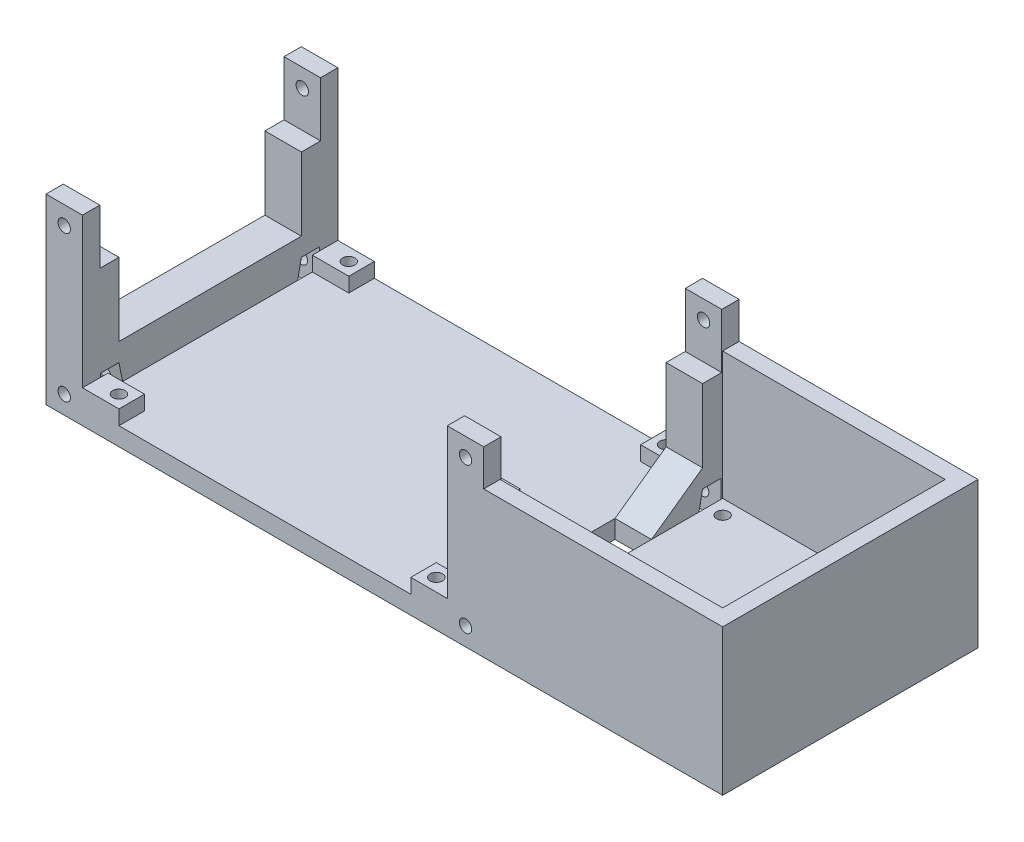
SolidWorks part; units mm, degrees
ref_plane "Front Plane" through (0, 0, 0) normal (0, 0, 1) x (1, 0, 0)
ref_plane "Top Plane" through (0, 0, 0) normal (0, 1, 0) x (1, 0, 0)
ref_plane "Right Plane" through (0, 0, 0) normal (1, 0, 0) x (0, 0, -1)
sketch "Sketch1" plane through (0, 0, 0) normal (0, 1, 0) x (1, 0, 0)
  line L1 (-60, -35) -> (60, -35)
  line L2 (-60, -35) -> (-60, 35)
  line L3 (-60, 35) -> (60, 35)
  line L4 (60, -35) -> (60, 35)
  line L5 (-60, -35) -> (60, 35) construction
  line L6 (-60, 35) -> (60, -35) construction
  point P0 (0, 0)
  dimension "D1" = 120
  dimension "D2" = 70
extrude "Boss-Extrude1" add sketch "Sketch1" along normal blind 5
sketch "Sketch4" plane through (0, 5, 0) normal (0, 1, 0) x (1, 0, 0)
  line L1 (-60, -35) -> (-50, -35)
  line L2 (-60, -35) -> (-60, -25)
  line L3 (-60, -25) -> (-50, -25)
  line L4 (-50, -35) -> (-50, -25)
  line L5 (-60, 35) -> (-50, 35)
  line L6 (-60, 35) -> (-60, 25)
  line L7 (-60, 25) -> (-50, 25)
  line L8 (-50, 35) -> (-50, 25)
  line L9 (60, -35) -> (50, -35)
  line L10 (60, -35) -> (60, -25)
  line L11 (60, -25) -> (50, -25)
  line L12 (50, -35) -> (50, -25)
  line L13 (60, 35) -> (50, 35)
  line L14 (60, 35) -> (60, 25)
  line L15 (60, 25) -> (50, 25)
  line L16 (50, 35) -> (50, 25)
  dimension "D1" = 10
  dimension "D2" = 10
extrude "Boss-Extrude2" add sketch "Sketch4" along normal blind 30
sketch "Sketch5" plane through (0, 0, 0) normal (0, -1, 0) x (1, 0, 0)
  line L0 (-60, -35) -> (-60, 35) construction
  line L1 (-60, -30) -> (-50, -30)
  line L2 (-60, -30) -> (-60, -25)
  line L3 (-60, -25) -> (-50, -25)
  line L4 (-50, -30) -> (-50, -25)
  line L5 (60, 35) -> (60, -35) construction
  line L6 (-60, 30) -> (-50, 30)
  line L7 (-60, 30) -> (-60, 25)
  line L8 (-60, 25) -> (-50, 25)
  line L9 (-50, 30) -> (-50, 25)
  line L10 (60, 30) -> (50, 30)
  line L11 (60, 30) -> (60, 25)
  line L12 (60, 25) -> (50, 25)
  line L13 (50, 30) -> (50, 25)
  line L14 (60, -35) -> (-60, -35) construction
  line L15 (60, -30) -> (50, -30)
  line L16 (60, -30) -> (60, -25)
  line L17 (60, -25) -> (50, -25)
  line L18 (50, -30) -> (50, -25)
  line L19 (-60, 35) -> (60, 35) construction
  dimension "D1" = 10
  dimension "D2" = 5
  dimension "D3" = 5
  dimension "D4" = 5
extrude "Cut-Extrude2" cut sketch "Sketch5" against normal blind 10
sketch "Sketch8" plane through (0, 5, 0) normal (0, 1, 0) x (1, 0, 0)
  line L1 (-50, 35) -> (-40, 35)
  line L2 (-50, 35) -> (-50, 28)
  line L3 (-50, 28) -> (-40, 28)
  line L4 (-40, 35) -> (-40, 28)
  line L5 (-50, -35) -> (-40, -35)
  line L6 (-50, -35) -> (-50, -28)
  line L7 (-50, -28) -> (-40, -28)
  line L8 (-40, -35) -> (-40, -28)
  line L9 (50, -35) -> (40, -35)
  line L10 (50, -35) -> (50, -28)
  line L11 (50, -28) -> (40, -28)
  line L12 (40, -35) -> (40, -28)
  line L13 (50, 35) -> (40, 35)
  line L14 (50, 35) -> (50, 28)
  line L15 (50, 28) -> (40, 28)
  line L16 (40, 35) -> (40, 28)
  dimension "D1" = 7
  dimension "D2" = 10
extrude "Boss-Extrude5" add sketch "Sketch8" along normal blind 4
hole_wizard "M3 Clearance Hole2" positions "Sketch10" profile "Sketch9" hole size "M3" standard "ANSI Metric"
sketch "Sketch10" plane through (0, 9, 0) normal (0, 1, 0) x (1, 0, 0)
  line L1 (40, -35) -> (50, -35) construction
  line L2 (-50, -30) -> (-50, -28) construction
  point P0 (-43.5, -31.5)
  point P2 (-43.5, 31.5)
  point P4 (43.5, 31.5)
  point P6 (43.5, -31.5)
  dimension "D1" = 87
  dimension "D2" = 63
  dimension "D3" = 3.5
  dimension "D4" = 6.5
sketch "Sketch9" plane through (-43.5, 9, 31.5) normal (1, 0, 0) x (0, 0, 1)
  line L0 (0, 0) -> (0, 66.0215)
  line L1 (0, 66.0215) -> (1.7, 65)
  line L2 (1.7, 65) -> (1.7, 0)
  line L5 (1.7, 0) -> (0, 0)
  line L10 (0, 66.0215) -> (-1.7, 65) construction
  line L11 (0, -6.35) -> (0, 107.95) construction
  dimension "Hole Dia." = 3.4
  dimension "Hole Depth" = 65
  dimension "Drill Angle" = 118
sketch "Sketch12" plane through (0, 0, 0) normal (0, -1, 0) x (1, 0, 0)
  line L1 (125.5, 35) -> (60, 35)
  line L2 (125.5, 35) -> (125.5, -35)
  line L3 (125.5, -35) -> (60, -35)
  line L4 (60, 35) -> (60, -35)
  line L5 (125.5, 35) -> (60, -35) construction
  line L6 (125.5, -35) -> (60, 35) construction
  line L7 (60, 25) -> (60, -25) construction
  point P0 (92.75, 0)
  dimension "D1" = 65.5
  dimension "D2" = 70
extrude "Boss-Extrude6" add sketch "Sketch12" against normal blind 5
sketch "Sketch13" plane through (0, 5, 0) normal (0, 1, 0) x (1, 0, 0)
  line L1 (60, 35) -> (125.5, 35)
  line L2 (60, 35) -> (60, 30.5)
  line L3 (60, 30.5) -> (121, 30.5)
  line L4 (125.5, -35) -> (125.5, 35)
  line L5 (125.5, 35) -> (125.5, -35) construction
  line L6 (60, -35) -> (125.5, -35)
  line L7 (60, -35) -> (60, -30.5)
  line L8 (60, -30.5) -> (121, -30.5)
  line L11 (121, 30.5) -> (121, -30.5)
  dimension "D1" = 61
  dimension "D2" = 4.5
  dimension "D3" = 4.5
extrude "Boss-Extrude7" add sketch "Sketch13" along normal blind 35
hole_wizard "M3 Clearance Hole3" positions "Sketch15" profile "Sketch14" hole size "M3" standard "ANSI Metric"
sketch "Sketch15" plane through (0, 5, 0) normal (0, 1, 0) x (1, 0, 0)
  line L0 (121, -30.5) -> (60, -30.5) construction
  line L2 (60, -30) -> (60, -25) construction
  point P0 (117, -26.5)
  point P2 (117, 26.5)
  point P4 (64, 26.5)
  point P6 (64, -26.5)
  point P15 (60, -27.5)
  dimension "D1" = 53
  dimension "D2" = 53
  dimension "D3" = 4
  dimension "D4" = 4
sketch "Sketch14" plane through (117, 5, 26.5) normal (1, 0, 0) x (0, 0, 1)
  line L0 (0, 0) -> (0, 66.0215)
  line L1 (0, 66.0215) -> (1.7, 65)
  line L2 (1.7, 65) -> (1.7, 0)
  line L5 (1.7, 0) -> (0, 0)
  line L10 (0, 66.0215) -> (-1.7, 65) construction
  line L11 (0, -6.35) -> (0, 107.95) construction
  dimension "Hole Dia." = 3.4
  dimension "Hole Depth" = 65
  dimension "Drill Angle" = 118
sketch "Sketch24" plane through (0, 5, 0) normal (0, 1, 0) x (1, 0, 0)
  line L1 (-60, 25) -> (-50, 25)
  line L2 (-60, 25) -> (-60, -25)
  line L3 (-60, -25) -> (-50, -25)
  line L4 (-50, 25) -> (-50, -25)
  line L5 (60, -25) -> (50, -25)
  line L6 (60, -25) -> (60, 25)
  line L7 (60, 25) -> (50, 25)
  line L8 (50, -25) -> (50, 25)
extrude "Boss-Extrude10" add sketch "Sketch24" along normal blind 10
sketch "Sketch16" plane through (0, 15, 0) normal (0, 1, 0) x (1, 0, 0)
  line L0 (50, 25) -> (50, -25) construction
  line L1 (60, -11) -> (50, -11)
  line L2 (60, -11) -> (60, 11)
  line L3 (60, 11) -> (50, 11)
  line L4 (50, -11) -> (50, 11)
  line L6 (60, -30) -> (60, -25) construction
  line L9 (60, -25) -> (50, -25) construction
  line L10 (50, 25) -> (60, 25) construction
  dimension "D1" = 14
  dimension "D2" = 14
extrude "Cut-Extrude5" cut sketch "Sketch16" against normal through all
sketch "Sketch22" plane through (0, 0, 35) normal (0, 0, 1) x (1, 0, 0)
  line L0 (-60, 0) -> (125.5, 0) construction
  line L2 (-60, 35) -> (-60, 0) construction
  line L3 (50, 35) -> (50, 9) construction
  circle A0 centre (-55, 5) radius 1.7
  circle A1 centre (55, 5) radius 1.7
  dimension "D3" = 3.4
  dimension "D1" = 5
  dimension "D2" = 5
  dimension "D4" = 5
extrude "Cut-Extrude7" cut sketch "Sketch22" against normal blind 20
chamfer "Chamfer2" distance 14 distance2 10 2 edges at (55, 15, 11) (55, 15, -11) first distance on face at (53.75, 15, 18) first distance on face at (56.25, 15, -18)
sketch "Sketch25" plane through (0, 0, 0) normal (0, -1, 0) x (1, 0, 0)
  line L0 (-60, 25) -> (-50, 25) construction
  line L1 (-57.745, -20) -> (-52.255, -20)
  line L2 (-57.745, -20) -> (-57.745, -17)
  line L3 (-57.745, -17) -> (-52.255, -17)
  line L4 (-52.255, -20) -> (-52.255, -17)
  line L5 (52.255, -20) -> (57.745, -20)
  line L6 (52.255, -20) -> (52.255, -17)
  line L7 (52.255, -17) -> (57.745, -17)
  line L8 (57.745, -20) -> (57.745, -17)
  line L9 (52.255, 20) -> (57.745, 20)
  line L10 (52.255, 20) -> (52.255, 17)
  line L11 (52.255, 17) -> (57.745, 17)
  line L12 (57.745, 20) -> (57.745, 17)
  line L13 (-57.745, 20) -> (-52.255, 20)
  line L14 (-57.745, 20) -> (-57.745, 17)
  line L15 (-57.745, 17) -> (-52.255, 17)
  line L16 (-52.255, 20) -> (-52.255, 17)
  line L17 (-50, -25) -> (-60, -25) construction
  line L18 (-50, -25) -> (-60, -25) construction
  line L23 (55, 25) -> (55, -25) construction
  line L24 (50, 25) -> (60, 25) construction
  line L25 (60, -25) -> (50, -25) construction
  line L26 (-55, 25) -> (-55, -25) construction
  line L27 (-60, 25) -> (-50, 25) construction
  dimension "D1" = 3
  dimension "D2" = 5
  dimension "D3" = 5
  dimension "D4" = 5.49
  dimension "D5" = 2.745
  dimension "D6" = 2.745
extrude "Cut-Extrude8" cut sketch "Sketch25" against normal blind 8
sketch "Sketch26" plane through (0, 0, -35) normal (0, 0, -1) x (-1, 0, 0)
  circle A0 centre (-55, 5) radius 1.7
  circle A1 centre (55, 5) radius 1.7
  circle A2 centre (55, 5) radius 1.7 construction
  circle A3 centre (-55, 5) radius 1.7 construction
extrude "Cut-Extrude9" cut sketch "Sketch26" against normal blind 20
sketch "Sketch28" plane through (-60, 0, 0) normal (-1, 0, 0) x (0, 0, 1)
  line L0 (-25, 10) -> (-23, 0)
  line L1 (-25, 0) -> (25, 0) construction
  line L2 (-23, 0) -> (-25, 0)
  line L3 (-25, 0) -> (-25, 10)
  line L4 (25, 10) -> (23, 0)
  line L5 (23, 0) -> (25, 0)
  line L6 (25, 10) -> (25, 0) construction
  line L7 (25, 0) -> (25, 10)
  dimension "D1" = 2
extrude "Cut-Extrude11" cut sketch "Sketch28" against normal blind 10
pattern_linear "LPattern1" count 2 spacing 110 along (1, 0, 0) of "Cut-Extrude11"
sketch "Sketch29" plane through (0, 35, 0) normal (0, 1, 0) x (1, 0, 0)
  line L1 (60, 35) -> (50, 35)
  line L2 (60, 35) -> (60, 30.25)
  line L3 (60, 30.25) -> (50, 30.25)
  line L4 (50, 35) -> (50, 30.25)
  line L6 (60, -35) -> (50, -35)
  line L7 (60, -35) -> (60, -30.25)
  line L8 (60, -30.25) -> (50, -30.25)
  line L9 (50, -35) -> (50, -30.25)
  line L11 (-50, 35) -> (-60, 35)
  line L12 (-50, 35) -> (-50, 30.25)
  line L13 (-50, 30.25) -> (-60, 30.25)
  line L14 (-60, 35) -> (-60, 30.25)
  line L16 (-50, -35) -> (-60, -35)
  line L17 (-50, -35) -> (-50, -30.25)
  line L18 (-50, -30.25) -> (-60, -30.25)
  line L19 (-60, -35) -> (-60, -30.25)
  line L20 (50, 35) -> (50, 25) construction
  line L21 (-60, 35) -> (-60, 25) construction
  dimension "D1" = 4.75
extrude "Boss-Extrude11" add sketch "Sketch29" along normal blind 15
sketch "Sketch31" plane through (0, 0, -35) normal (0, 0, -1) x (-1, 0, 0)
  line L0 (-50, 50) -> (-50, 9) construction
  line L1 (-60, 50) -> (-50, 50) construction
  line L2 (50, 50) -> (50, 9) construction
  circle A0 centre (-55, 45) radius 1.7
  circle A1 centre (55, 45) radius 1.7
  dimension "D1" = 3.4
  dimension "D2" = 5
  dimension "D3" = 5
  dimension "D4" = 5
extrude "Cut-Extrude13" cut sketch "Sketch31" against normal through all
sketch "Sketch33" plane through (-60, 0, 0) normal (-1, 0, 0) x (0, 0, 1)
  line L0 (-23, 0) -> (23, 0) construction
  line L1 (-20, 0) -> (20, 0)
  line L2 (-20, 0) -> (-20, 5)
  line L3 (-20, 5) -> (20, 5)
  line L4 (20, 0) -> (20, 5)
  line L5 (-23, 0) -> (-20, 0)
  line L6 (20, 0) -> (23, 0)
  dimension "D1" = 5
  dimension "D2" = 40
ref_plane "Plane1" through (-49, 92, 35) normal (0, 0, -1) x (-1, 0, 0)
equation "\"D5@Sketch25\"=\"D4@Sketch25\"/2"
equation "\"D6@Sketch25\"=\"D5@Sketch25\""
